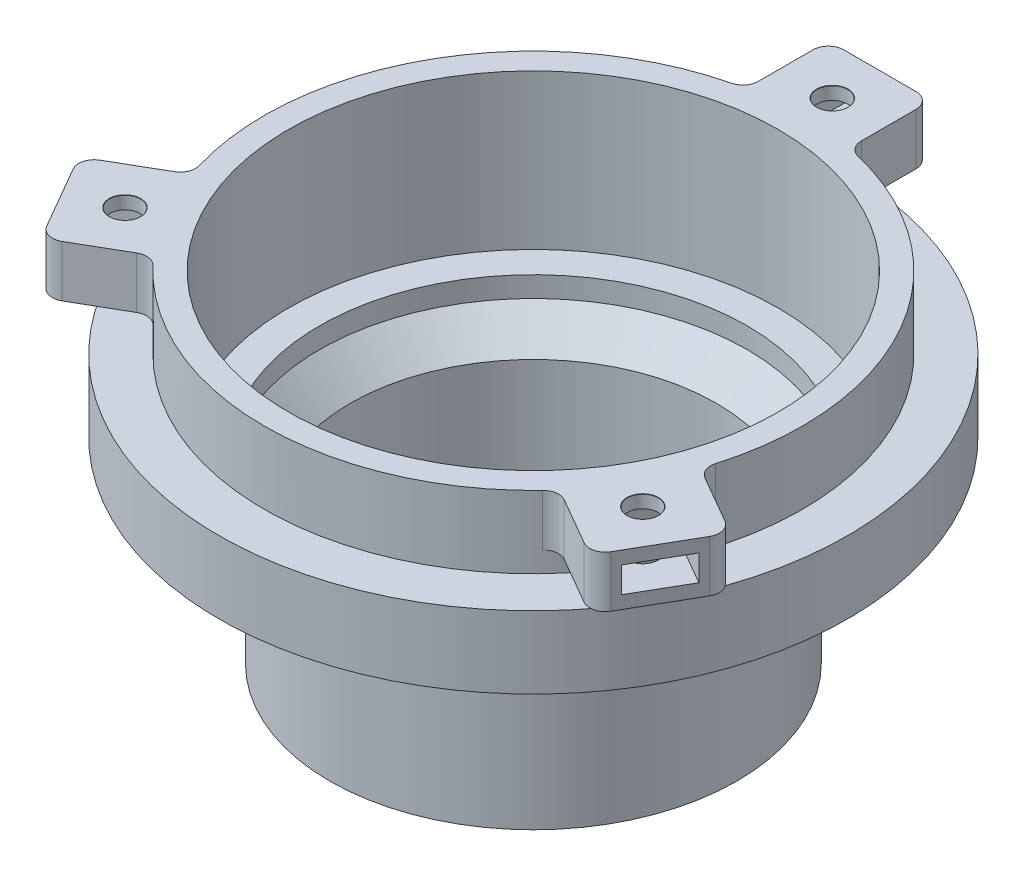
SolidWorks part; units mm, degrees
ref_plane "Plan de face" through (0, 0, 0) normal (0, 0, 1) x (1, 0, 0)
ref_plane "Plan de dessus" through (0, 0, 0) normal (0, 1, 0) x (1, 0, 0)
ref_plane "Plan de droite" through (0, 0, 0) normal (1, 0, 0) x (0, 0, -1)
sketch "Sketch1" plane through (0, 0, 0) normal (0, 0, 1) x (1, 0, 0)
  line L0 (17.75, 0) -> (17.75, 13)
  line L1 (17.75, 13) -> (20.75, 16)
  line L2 (20.75, 16) -> (20.75, 18)
  line L3 (20.75, 18) -> (23.75, 18)
  line L4 (23.75, 18) -> (23.75, 33)
  line L5 (26.1, 26) -> (30.5, 26)
  line L6 (30.5, 26) -> (30.5, 19)
  line L7 (30.5, 19) -> (28.5, 19)
  line L8 (0, -2.2363) -> (0, 22.2136) construction
  line L9 (28.5, 19) -> (28.5, 24)
  line L10 (28.5, 24) -> (26.1, 24)
  line L11 (26.1, 24) -> (26.1, 16)
  line L12 (17.75, 0) -> (19.75, 0)
  line L13 (19.75, 0) -> (19.75, 12.1716)
  line L14 (19.75, 12.1716) -> (22.75, 15.1716)
  line L15 (22.75, 15.1716) -> (22.75, 16)
  line L16 (22.75, 16) -> (26.1, 16)
  line L18 (23.75, 33) -> (26.1, 33)
  line L19 (26.1, 33) -> (26.1, 26)
  point P6 (0, 0)
  point P22 (23.75, 42.9983)
  dimension "D1" = 35.5
  dimension "D3" = 47.5
  dimension "D4" = 57
  dimension "D5" = 52.2
  dimension "D2" = 13
  dimension "D6" = 2
  dimension "D7" = 3
  dimension "D8" = 3
  dimension "D9" = 7
  dimension "D10" = 15
  dimension "D11" = 5
  dimension "D12" = 2
  dimension "D13" = 2
  dimension "D14" = 2
  dimension "D15" = 2
  dimension "D16" = 2
  dimension "D17" = 2
revolve "Revolve1" add sketch "Sketch1" angle 360 about L8
sketch "Sketch2" plane through (0, 33, 0) normal (0, 1, 0) x (1, 0, 0)
  line L0 (0, 0) -> (0, 33.6166) construction
  line L9 (-5, 33.6166) -> (-5, 25.6166)
  line L10 (-5, 25.6166) -> (5, 25.6166)
  line L11 (5, 25.6166) -> (5, 33.6166)
  line L18 (-5, 33.6166) -> (5, 33.6166)
  circle A7 centre (0, 0) radius 26.1 construction
  circle A10 centre (0, 0) radius 26.1 construction
  point P2 (4.726, 25.6686)
  point P10 (0, 33.6166)
  dimension "D1" = 10
  dimension "D3" = 8
extrude "Boss-Extrude1" add sketch "Sketch2" against normal blind 5
sketch "Sketch3" plane through (0, 33, 0) normal (0, 1, 0) x (1, 0, 0)
  line L0 (0, 0) -> (0, 29) construction
  line L2 (0, 0) -> (25.1147, -14.5) construction
  line L4 (0, 0) -> (-25.1147, -14.5) construction
  point P0 (0, 29)
  point P4 (-25.1147, -14.5)
  point P6 (25.1147, -14.5)
  point P26 (24.3314, -14.0477)
  dimension "D1" = 120
  dimension "D2" = 120
  dimension "D3" = 29
hole_wizard "Ø3.0 mm Dowel Holes2" positions "Sketch3" profile "Sketch4" hole size "Ø3.0" standard "ANSI Metric"
sketch "Sketch4" plane through (0, 33, -29) normal (1, 0, 0) x (0, 0, 1)
  line L0 (0, 0) -> (0, 5.9013)
  line L1 (0, 5.9013) -> (1.5, 5)
  line L2 (1.5, 5) -> (1.5, 0.025)
  line L3 (1.5, 0.025) -> (1.525, 0)
  line L5 (1.525, 0) -> (0, 0)
  line L6 (-1.5, 0.025) -> (-1.525, 0) construction
  line L10 (0, 5.9013) -> (-1.5, 5) construction
  line L11 (0, -6.35) -> (0, 107.95) construction
  dimension "Hole Dia." = 3
  dimension "Hole Depth" = 5
  dimension "Near C'Sink Dia." = 3.05
  dimension "Near C'Sink Angle" = 90
  dimension "Drill Angle" = 118
sketch "Sketch7" plane through (0, 0, -33.6166) normal (0, 0, -1) x (-1, 0, 0)
  line L0 (5, 28) -> (5, 33) construction
  line L1 (-2.75, 31.75) -> (2.75, 31.75)
  line L2 (-2.75, 31.75) -> (-2.75, 29.25)
  line L3 (-2.75, 29.25) -> (2.75, 29.25)
  line L4 (2.75, 31.75) -> (2.75, 29.25)
  line L5 (-2.75, 31.75) -> (2.75, 29.25) construction
  line L6 (-2.75, 29.25) -> (2.75, 31.75) construction
  line L7 (-5, 28) -> (5, 28) construction
  point P0 (0, 30.5)
  point P7 (5, 30.5)
  point P10 (0, 28)
  dimension "D1" = 2.5
  dimension "D2" = 5.5
extrude "Cut-Extrude2" cut sketch "Sketch7" against normal blind 7
pattern_circular "CirPattern1" count 3 every 120 about axis through (0, -2.2363, 0) along (0, -1, 0) of "Boss-Extrude1", "Ø3.0 mm Dowel Holes2", "Cut-Extrude2"
fillet "Fillet1" radius 1.5 12 edges at (-5, 30.5, -25.6166) (-5, 30.5, -33.6166) (5, 30.5, -33.6166) (5, 30.5, -25.6166) (24.6846, 30.5, 8.4782) (31.6128, 30.5, 12.4782) (19.6846, 30.5, 17.1384) (-19.6846, 30.5, 17.1384) (-26.6128, 30.5, 21.1384) (-31.6128, 30.5, 12.4782) (-24.6846, 30.5, 8.4782) (26.6128, 30.5, 21.1384)
equation "\"D15@Sketch1\"=\"D14@Sketch1\""
equation "\"D16@Sketch1\"=\"D14@Sketch1\""
equation "\"D17@Sketch1\"=\"D14@Sketch1\""
